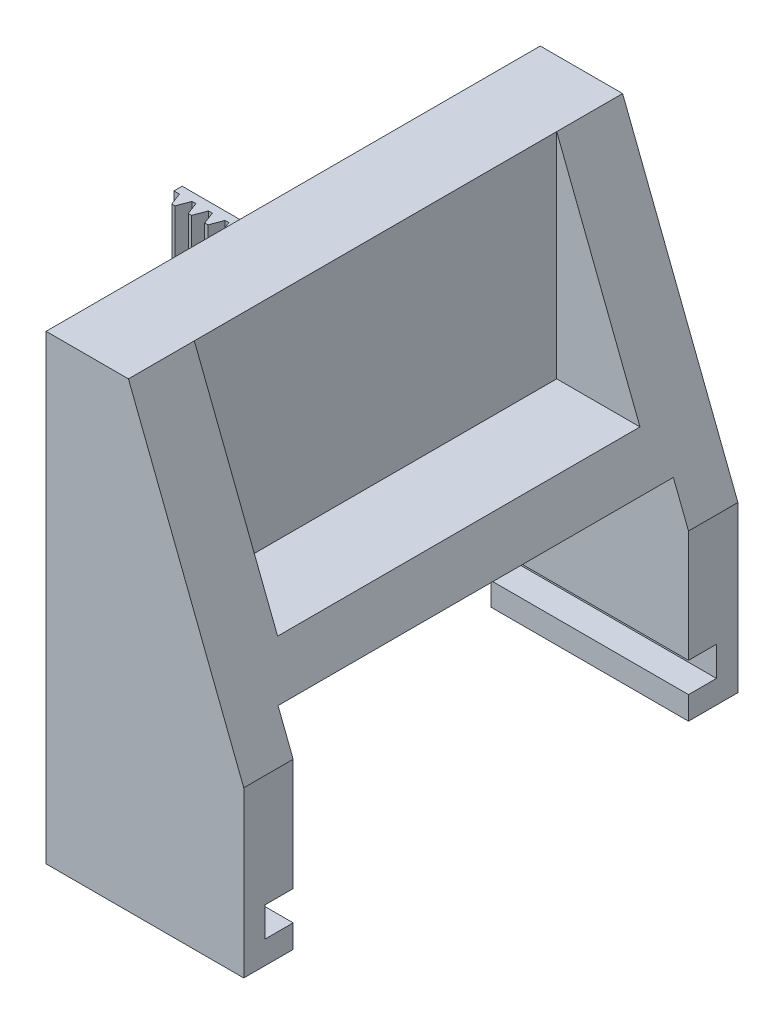
SolidWorks part; units mm, degrees
ref_plane "Front Plane" through (0, 0, 0) normal (0, 0, 1) x (1, 0, 0)
ref_plane "Top Plane" through (0, 0, 0) normal (0, 1, 0) x (1, 0, 0)
ref_plane "Right Plane" through (0, 0, 0) normal (1, 0, 0) x (0, 0, -1)
sketch "Sketch1" plane through (0, 0, 0) normal (0, 0, 1) x (1, 0, 0)
  line L0 (0, 0) -> (0, -28)
  line L1 (0, -28) -> (12, -28)
  line L2 (12, -28) -> (12, -18)
  line L3 (12, -18) -> (5, 0)
  line L4 (5, 0) -> (0, 0)
  dimension "D1" = 28
  dimension "D2" = 12
  dimension "D3" = 10
  dimension "D4" = 5
extrude "Boss-Extrude1" add sketch "Sketch1" against normal blind 30
sketch "Sketch4" plane through (0, 0, 0) normal (-1, 0, 0) x (0, 0, 1)
  line L0 (-30, 0) -> (-30, -28) construction
  line L1 (-27, -15.6386) -> (-3, -15.6386)
  line L2 (-27, -15.6386) -> (-27, -29.6386)
  line L3 (-27, -29.6386) -> (-3, -29.6386)
  line L4 (-3, -15.6386) -> (-3, -29.6386)
  point P4 (-27, -22.6386)
  dimension "D1" = 24
  dimension "D2" = 14
  dimension "D3" = 3
extrude "Cut-Extrude2" cut sketch "Sketch4" against normal blind 25 contours L2 L1 L4 L3
sketch "Sketch5" plane through (0, 0, 0) normal (-1, 0, 0) x (0, 0, 1)
  line L0 (-3, -15.6386) -> (-3, -28) construction
  line L1 (-3, -24.8) -> (-1.3, -24.8)
  line L2 (-3, -24.8) -> (-3, -26.6)
  line L3 (-3, -26.6) -> (-1.3, -26.6)
  line L4 (-1.3, -24.8) -> (-1.3, -26.6)
  line L5 (-3, -28) -> (0, -28) construction
  dimension "D1" = 1.8
  dimension "D2" = 1.7
  dimension "D3" = 1.4
extrude "Cut-Extrude3" cut sketch "Sketch5" against normal blind 15
ref_plane "Plane1" through (0, 0, -15) normal (0, 0, 1) x (1, 0, 0)
mirror "Mirror1" about plane through (0, 0, -15) normal (0, 0, 1) of "Cut-Extrude3"
sketch "Sketch6" plane through (0, 0, -15) normal (0, 0, 1) x (1, 0, 0)
  line L0 (5, 0) -> (5, -13)
  line L1 (5, -13) -> (10.0556, -13)
  line L2 (12, -18) -> (5, 0) construction
  line L3 (10.0556, -13) -> (5, 0)
  dimension "D1" = 13
extrude "Cut-Extrude4" cut sketch "Sketch6" against normal mid plane 22
ref_plane "Plane2" through (0, -15, 0) normal (0, 1, 0) x (1, 0, 0)
sketch "Sketch7" plane through (0, -15, 0) normal (0, 1, 0) x (1, 0, 0)
  line L0 (0, 22.7609) -> (-14.5, 22.7609)
  line L1 (0, 30) -> (0, 0) construction
  line L2 (-14.5, 22.7609) -> (-14.5, 22.2609)
  line L3 (0, 22.7609) -> (0, 22.2609)
  line L4 (0, 22.2609) -> (-0.4, 22.2609)
  line L5 (-0.8812, 21.5119) -> (-1.1644, 22.2609)
  line L6 (-0.4, 22.2609) -> (-0.6812, 21.5119)
  line L7 (-0.6812, 21.5119) -> (-0.8812, 21.5119)
  line L8 (-1.8812, 21.5119) -> (-2.1644, 22.2609)
  line L9 (-1.6812, 21.5119) -> (-1.8812, 21.5119)
  line L10 (-1.4, 22.2609) -> (-1.6812, 21.5119)
  line L11 (-2.8812, 21.5119) -> (-3.1644, 22.2609)
  line L12 (-2.6812, 21.5119) -> (-2.8812, 21.5119)
  line L13 (-2.4, 22.2609) -> (-2.6812, 21.5119)
  line L14 (-3.8812, 21.5119) -> (-4.1644, 22.2609)
  line L15 (-3.6812, 21.5119) -> (-3.8812, 21.5119)
  line L16 (-3.4, 22.2609) -> (-3.6812, 21.5119)
  line L17 (-4.8812, 21.5119) -> (-5.1644, 22.2609)
  line L18 (-4.6812, 21.5119) -> (-4.8812, 21.5119)
  line L19 (-4.4, 22.2609) -> (-4.6812, 21.5119)
  line L20 (-5.8812, 21.5119) -> (-6.1644, 22.2609)
  line L21 (-5.6812, 21.5119) -> (-5.8812, 21.5119)
  line L22 (-5.4, 22.2609) -> (-5.6812, 21.5119)
  line L23 (-6.8812, 21.5119) -> (-7.1644, 22.2609)
  line L24 (-6.6812, 21.5119) -> (-6.8812, 21.5119)
  line L25 (-6.4, 22.2609) -> (-6.6812, 21.5119)
  line L26 (-7.8812, 21.5119) -> (-8.1644, 22.2609)
  line L27 (-7.6812, 21.5119) -> (-7.8812, 21.5119)
  line L28 (-7.4, 22.2609) -> (-7.6812, 21.5119)
  line L29 (-8.8812, 21.5119) -> (-9.1644, 22.2609)
  line L30 (-8.6812, 21.5119) -> (-8.8812, 21.5119)
  line L31 (-8.4, 22.2609) -> (-8.6812, 21.5119)
  line L32 (-9.8812, 21.5119) -> (-10.1644, 22.2609)
  line L33 (-9.6812, 21.5119) -> (-9.8812, 21.5119)
  line L34 (-9.4, 22.2609) -> (-9.6812, 21.5119)
  line L35 (-10.8812, 21.5119) -> (-11.1644, 22.2609)
  line L36 (-10.6812, 21.5119) -> (-10.8812, 21.5119)
  line L37 (-10.4, 22.2609) -> (-10.6812, 21.5119)
  line L38 (-11.8812, 21.5119) -> (-12.1644, 22.2609)
  line L39 (-11.6812, 21.5119) -> (-11.8812, 21.5119)
  line L40 (-11.4, 22.2609) -> (-11.6812, 21.5119)
  line L41 (-12.8812, 21.5119) -> (-13.1644, 22.2609)
  line L42 (-12.6812, 21.5119) -> (-12.8812, 21.5119)
  line L43 (-12.4, 22.2609) -> (-12.6812, 21.5119)
  line L44 (-13.8812, 21.5119) -> (-14.1644, 22.2609)
  line L45 (-13.6812, 21.5119) -> (-13.8812, 21.5119)
  line L46 (-13.4, 22.2609) -> (-13.6812, 21.5119)
  line L47 (-0.8812, 21.5119) -> (-1.8812, 21.5119) construction
  line L48 (-1.1644, 22.2609) -> (-1.4, 22.2609)
  line L49 (-2.1644, 22.2609) -> (-2.4, 22.2609)
  line L50 (-3.1644, 22.2609) -> (-3.4, 22.2609)
  line L51 (-4.1644, 22.2609) -> (-4.4, 22.2609)
  line L52 (-5.1644, 22.2609) -> (-5.4, 22.2609)
  line L53 (-6.1644, 22.2609) -> (-6.4, 22.2609)
  line L54 (-7.1644, 22.2609) -> (-7.4, 22.2609)
  line L55 (-8.1644, 22.2609) -> (-8.4, 22.2609)
  line L56 (-9.1644, 22.2609) -> (-9.4, 22.2609)
  line L57 (-10.1644, 22.2609) -> (-10.4, 22.2609)
  line L58 (-11.1644, 22.2609) -> (-11.4, 22.2609)
  line L59 (-12.1644, 22.2609) -> (-12.4, 22.2609)
  line L60 (-13.1644, 22.2609) -> (-13.4, 22.2609)
  line L61 (-14.1644, 22.2609) -> (-14.5, 22.2609)
  dimension "D1" = 0.8
  dimension "D4" = 0.2
  dimension "D2" = 14.5
  dimension "D3" = 0.5
  dimension "D5" = 1
  dimension "D6" = 0.4
extrude "Boss-Extrude2" add sketch "Sketch7" along normal blind 4
